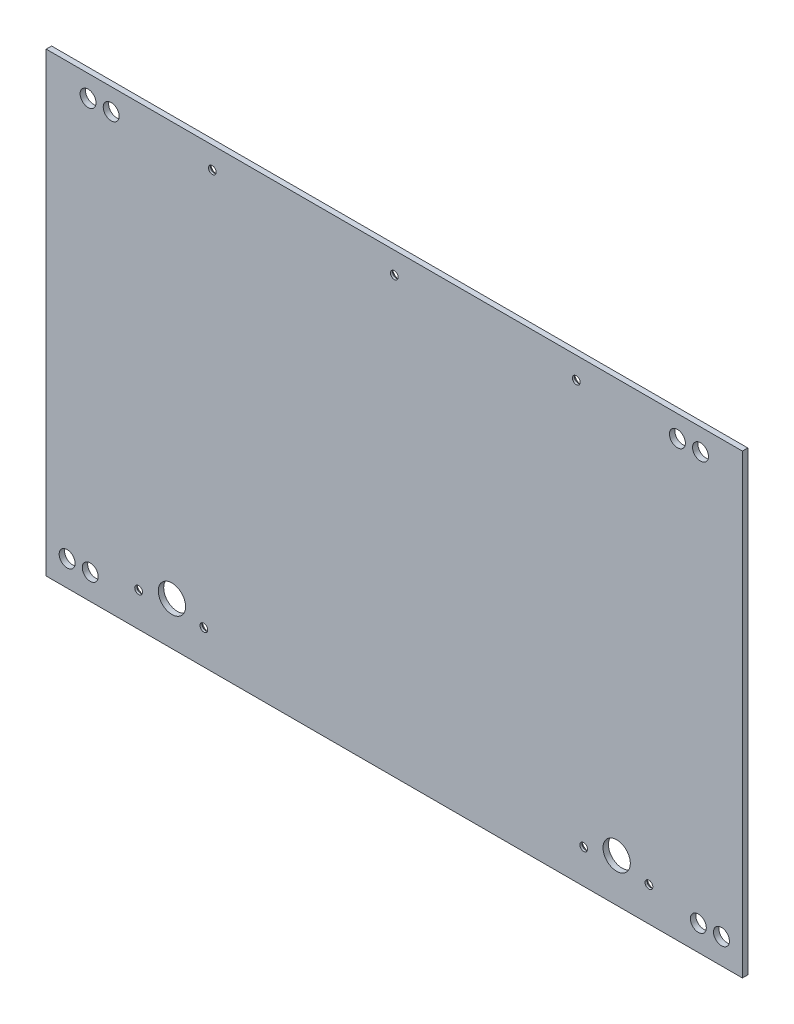
SolidWorks part; units mm, degrees
material "ABS"
ref_plane "X-Y Datum" through (0, 0, 0) normal (0, 0, 1) x (1, 0, 0)
ref_plane "X-Z Datum" through (0, 0, 0) normal (0, 1, 0) x (1, 0, 0)
ref_plane "Y-Z Datum" through (0, 0, 0) normal (1, 0, 0) x (0, 0, -1)
sketch "Sketch1" plane through (0, 0, 0) normal (0, 0, 1) x (1, 0, 0)
  line L0 (-153.025, 98.7125) -> (-153.025, -98.7125)
  line L1 (-153.025, 98.7125) -> (153.025, 98.7125)
  line L2 (-153.025, 98.7125) -> (-153.025, -98.7125)
  line L3 (-153.025, -98.7125) -> (153.025, -98.7125)
  line L4 (153.025, 98.7125) -> (153.025, -98.7125)
  line L5 (-153.025, 98.7125) -> (153.025, -98.7125) construction
  line L6 (-153.025, -98.7125) -> (153.025, 98.7125) construction
  line L7 (-153.025, -98.7125) -> (153.025, -98.7125)
  line L8 (153.025, 98.7125) -> (153.025, -98.7125)
  line L9 (-153.025, 98.7125) -> (153.025, 98.7125)
  circle A0 centre (-142.25, -87.9375) radius 10.775
  circle A1 centre (-118.25, -87.9375) radius 10.775 construction
  circle A2 centre (-130.25, -64.9375) radius 10.775
  point P0 (0, 0)
  dimension "D1" = 21.55
  dimension "D2" = 24
  dimension "D3" = 23
  dimension "D4" = 12
  dimension "D5" = 197.425
  dimension "D6" = 306.05
  dimension "D7" = 0
extrude "Boss-Extrude1" add sketch "Sketch1" along normal blind 2.3813 contours A0 L3 L4 L1 L2 A2 | A2 | A0 | A0 L2 L3 | L9 L0 L7 L8 L1 L4 L3 L2 region at (1.7287, 0.9747, 0) region at (-150.6182, -96.3057, 0) region at (-142.25, -87.9375, 0) region at (-130.25, -64.9375, 0)
sketch "Sketch9" plane through (0, 98.7125, 0) normal (0, 1, 0) x (1, 0, 0)
  line L4 (153.025, 0) -> (-153.025, 0)
  line L5 (-153.025, 0) -> (-153.025, -2.3813)
  line L6 (-153.025, -2.3813) -> (153.025, -2.3813)
  line L7 (153.025, -2.3813) -> (153.025, 0)
  line L8 (153.025, 0) -> (-153.025, 0)
  line L9 (-153.025, 0) -> (-153.025, -2.3813)
  line L10 (-153.025, -2.3813) -> (153.025, -2.3813)
  line L11 (153.025, -2.3813) -> (153.025, 0)
  dimension "D1" = 0
extrude "Boss-Extrude2" add sketch "Sketch9" along normal blind 3.175
sketch "Sketch10" plane through (0, 0, 0) normal (0, 0, -1) x (-1, 0, 0)
  circle A0 centre (-134.61, 92.3625) radius 3.5
  circle A1 centre (-124.45, 92.3625) radius 3.5
  circle A2 centre (-143.8175, -87.5375) radius 3.5
  circle A3 centre (-133.6575, -87.5375) radius 3.5
  point P1 (-133.6575, -87.5375)
  dimension "D1" = 7
extrude "Cut-Extrude1" cut sketch "Sketch10" against normal through all
mirror "Mirror1" about plane through (0, 0, 0) normal (1, 0, 0) of "Cut-Extrude1"
sketch "Sketch11" plane through (0, 0, 0) normal (0, 0, -1) x (-1, 0, 0)
  point P0 (-111.94, -83.7125)
  point P1 (-83.25, -83.7125)
  point P5 (-80, 92.3625)
  point P7 (0, 92.3625)
  point P9 (80, 92.3625)
  point P13 (112.402, -83.7125)
  point P15 (83.712, -83.7125)
hole_wizard "CSK for M3 Flat Head Machine Screw1" positions "Sketch11" profile "Sketch12" countersink size "M3" standard "ANSI Metric" end condition through all
sketch "Sketch12" plane through (111.94, -83.7125, 0) normal (1, 0, 0) x (0, 1, 0)
  line L0 (0, 0) -> (0, 2.3812)
  line L1 (0, 2.3812) -> (1.7, 2.3812)
  line L2 (1.7, 2.3812) -> (1.7, 1.45)
  line L3 (1.7, 1.45) -> (3.15, 0)
  line L5 (3.15, 0) -> (0, 0)
  line L6 (-1.7, 1.45) -> (-3.15, 0) construction
  line L11 (0, -6.35) -> (0, 107.95) construction
  dimension "Thru Hole Dia." = 3.4
  dimension "Thru Hole Depth" = 2.3813
  dimension "Near C'Sink Dia." = 6.3
  dimension "Near C'Sink Angle" = 90
sketch "Sketch13" plane through (0, 0, 0) normal (0, 0, -1) x (-1, 0, 0)
  circle A0 centre (-97.75, -79.7125) radius 6 construction
  circle A1 centre (97.75, -79.7125) radius 6 construction
  circle A2 centre (-97.75, -79.7125) radius 6
  circle A3 centre (97.75, -79.7125) radius 6
extrude "Cut-Extrude2" cut sketch "Sketch13" against normal through all
